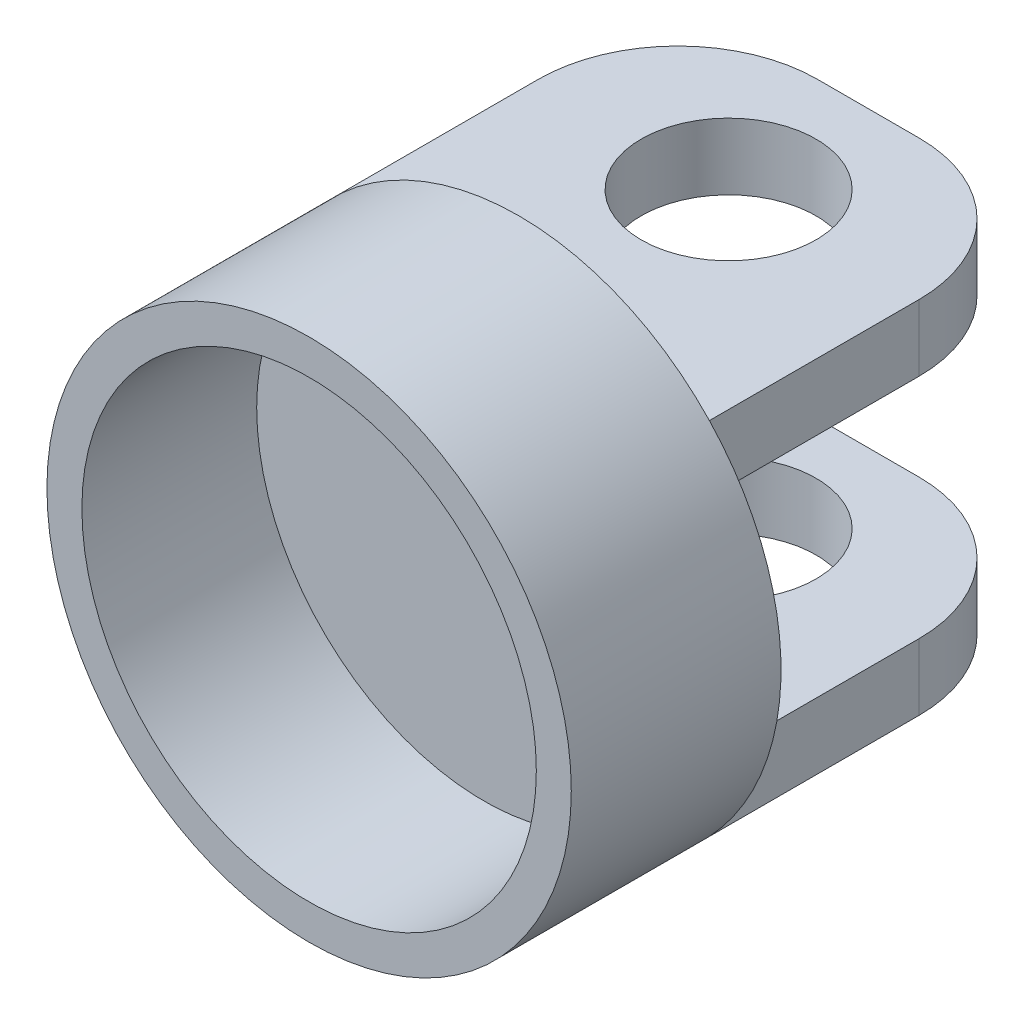
SolidWorks part; units mm, degrees
ref_plane "Front Plane" through (0, 0, 0) normal (0, 0, 1) x (1, 0, 0)
ref_plane "Top Plane" through (0, 0, 0) normal (0, 1, 0) x (1, 0, 0)
ref_plane "Right Plane" through (0, 0, 0) normal (1, 0, 0) x (0, 0, -1)
sketch "Sketch1" plane through (0, 0, 0) normal (0, 0, 1) x (1, 0, 0)
  circle A0 centre (0, 0) radius 15
  circle A1 centre (0, 0) radius 13
  dimension "D1" = 26
  dimension "D2" = 30
extrude "Boss-Extrude1" add sketch "Sketch1" along normal blind 10
extrude "Boss-Extrude2" add sketch "Sketch1<2>" along normal blind 10
sketch "Sketch1<2>" plane through (0, 0, 0) normal (0, 0, 1) x (1, 0, 0) same geometry as "Sketch1"
sketch "Sketch2" plane through (0, 0, 0) normal (0, 0, -1) x (-1, 0, 0)
  circle A0 centre (0, 0) radius 15 construction
  circle A1 centre (0, 0) radius 15
extrude "Boss-Extrude3" add sketch "Sketch2" along normal blind 2
sketch "Sketch3" plane through (0, 0, -2) normal (0, 0, -1) x (-1, 0, 0)
  line L0 (-15, 0) -> (15, 0) construction
  line L1 (0, -8.4015) -> (0, 8.4015)
  line L3 (-10.9018, -6.5) -> (10.9018, -6.5)
  line L4 (-10.9018, -6.5) -> (-10.9018, -10.303)
  line L5 (-10.9018, -10.303) -> (10.9018, -10.303)
  line L6 (10.9018, -6.5) -> (10.9018, -10.303)
  line L7 (-10.9018, -6.5) -> (10.9018, -10.303) construction
  line L8 (-10.9018, -10.303) -> (10.9018, -6.5) construction
  line L9 (-10.9018, 6.5) -> (10.9018, 6.5)
  line L10 (-10.9018, 6.5) -> (-10.9018, 10.303)
  line L11 (-10.9018, 10.303) -> (10.9018, 10.303)
  line L12 (10.9018, 6.5) -> (10.9018, 10.303)
  line L13 (-10.9018, 6.5) -> (10.9018, 10.303) construction
  line L14 (-10.9018, 10.303) -> (10.9018, 6.5) construction
  circle A0 centre (0, 0) radius 15 construction
  point P8 (0, 0)
  dimension "D1" = 13
extrude "Boss-Extrude4" add sketch "Sketch3" along normal blind 20 contours L6 L3 L4 L5 | L9 L12 L11 L10 region at (5.4509, 6.7213, -2) region at (-5.4509, -6.7213, -2)
fillet "Fillet1" radius 8 4 edges at (10.9018, 8.4015, -22) (10.9018, -8.4015, -22) (-10.9018, 8.4015, -22) (-10.9018, -8.4015, -22)
sketch "Sketch4" plane through (0, 10.303, 0) normal (0, 1, 0) x (1, 0, 0)
  line L0 (2.9018, 22) -> (-2.9018, 22) construction
  circle A0 centre (0, 14) radius 5
  point P4 (0, 22)
  dimension "D2" = 10
  dimension "D1" = 8
extrude "Cut-Extrude1" cut sketch "Sketch4" against normal up to surface (20.6059 mm away) up to face at (0, -10.303, -13.219)
